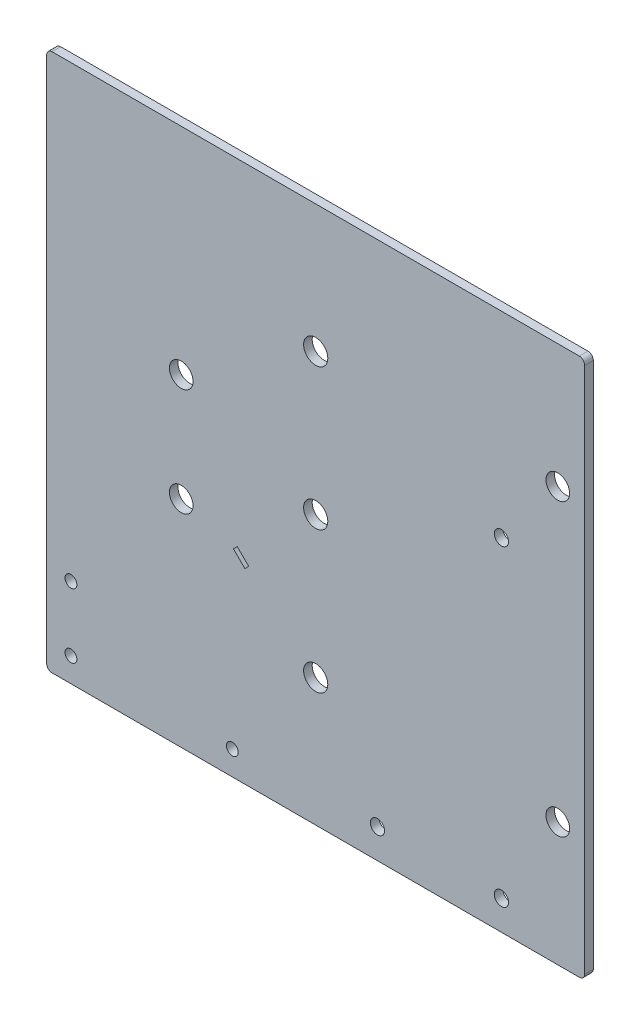
SolidWorks part; units mm, degrees
material "FR4_stuffedProtoboard"
ref_plane "Front Plane" through (0, 0, 0) normal (0, 0, 1) x (1, 0, 0)
ref_plane "Top Plane" through (0, 0, 0) normal (0, 1, 0) x (1, 0, 0)
ref_plane "Right Plane" through (0, 0, 0) normal (1, 0, 0) x (0, 0, -1)
sketch "Sketch1" plane through (0, 0, 0) normal (0, 0, 1) x (1, 0, 0)
  line L1 (-50, -50) -> (50, -50)
  line L2 (-50, -50) -> (-50, 50)
  line L3 (-50, 50) -> (50, 50)
  line L4 (50, -50) -> (50, 50)
  line L5 (-50, -50) -> (50, 50) construction
  line L6 (-50, 50) -> (50, -50) construction
  dimension "D1" = 100
extrude "Boss-Extrude1" add sketch "Sketch1" along normal blind 1.6
sketch "Sketch2" [suppressed] plane through (0, 0, 1.6) normal (0, 0, 1) x (1, 0, 0)
  circle A0 centre (0, 0) radius 50
  line M2 (50, -50) -> (50, 50)
  line M3 (50, 50) -> (-50, 50)
  line M4 (-50, 50) -> (-50, -50)
  line M5 (-50, -50) -> (50, -50)
  dimension "D1" = 100
extrude "Cut-Extrude1" [suppressed] cut sketch "Sketch2" against normal blind 1.6 contours A0 M3 M4 | A0 M4 M5 | A0 M5 M2 | A0 M2 M3
sketch "Sketch3" plane through (0, 0, 1.6) normal (0, 0, -1) x (-1, 0, 0)
  line L0 (-40, -22) -> (-50, -22) construction
  line L1 (-40, -32) -> (-40, -22) construction
  line L2 (-50, -32) -> (-40, -32) construction
  line L3 (-50, -22) -> (-50, -32) construction
  line L4 (-40, -22) -> (-50, -22)
  line L5 (-40, -32) -> (-40, -22)
  line L6 (-50, -32) -> (-40, -32)
  line L7 (-50, -22) -> (-50, -32)
  line L8 (-40, 22) -> (-40, 32) construction
  line L9 (-40, 32) -> (-50, 32) construction
  line L10 (-50, 32) -> (-50, 22) construction
  line L11 (-50, 22) -> (-40, 22) construction
  line L12 (-40, 22) -> (-40, 32)
  line L13 (-40, 32) -> (-50, 32)
  line L14 (-50, 32) -> (-50, 22)
  line L15 (-50, 22) -> (-40, 22)
  line L16 (5, -22) -> (-5, -22) construction
  line L17 (5, -32) -> (5, -22) construction
  line L18 (-5, -32) -> (5, -32) construction
  line L19 (-5, -22) -> (-5, -32) construction
  line L20 (5, -22) -> (-5, -22)
  line L21 (5, -32) -> (5, -22)
  line L22 (-5, -32) -> (5, -32)
  line L23 (-5, -22) -> (-5, -32)
  line L24 (5, 22) -> (5, 32) construction
  line L25 (5, 32) -> (-5, 32) construction
  line L26 (-5, 32) -> (-5, 22) construction
  line L27 (-5, 22) -> (5, 22) construction
  line L28 (5, 22) -> (5, 32)
  line L29 (5, 32) -> (-5, 32)
  line L30 (-5, 32) -> (-5, 22)
  line L31 (-5, 22) -> (5, 22)
  line L32 (17, 25) -> (45, 25) construction
  line L33 (45, 25) -> (45, -25) construction
  line L34 (17, -25) -> (45, -25) construction
  line L35 (17, 25) -> (17, -25) construction
  line L36 (17, 25) -> (45, 25)
  line L37 (45, 25) -> (45, -25)
  line L38 (17, -25) -> (45, -25)
  line L39 (17, 25) -> (17, -25)
  circle A0 centre (0, 26.25) radius 2.2479 construction
  circle A2 centre (0, 26.25) radius 2.2479
  circle A3 centre (0, 0) radius 2.2479
  circle A4 centre (-34.525, -44.525) radius 1.325 construction
  circle A6 centre (-34.525, -44.525) radius 1.325
  circle A8 centre (0, -26.25) radius 2.2479 construction
  circle A9 centre (0, -26.25) radius 2.2479
  circle A11 centre (-45, -27) radius 2.2
  circle A13 centre (-45, 27) radius 2.2
  circle A14 centre (-34.525, 13.525) radius 1.325 construction
  circle A15 centre (-34.525, 13.525) radius 1.325
  circle A16 centre (15.5, -45.5) radius 1.1 construction
  circle A17 centre (15.5, -45.5) radius 1.1
  circle A18 centre (45.5, -45.5) radius 1.1 construction
  circle A19 centre (45.5, -45.5) radius 1.1
  circle A20 centre (45.5, -33.5) radius 1.1 construction
  circle A21 centre (45.5, -33.5) radius 1.1
  circle A22 centre (-11.475, -44.525) radius 1.325 construction
  circle A23 centre (-11.475, -44.525) radius 1.325
  circle A24 centre (25, -10) radius 2.2 construction
  circle A25 centre (25, -10) radius 2.2
  circle A26 centre (25, 10) radius 2.2 construction
  circle A27 centre (25, 10) radius 2.2
  circle A28 centre (-45, 27) radius 2.2 construction
  circle A29 centre (-45, 27) radius 2.2
  circle A30 centre (-45, -27) radius 2.2 construction
  circle A31 centre (-45, -27) radius 2.2
  dimension "D1" = 4.4958
extrude "Cut-Extrude2" cut sketch "Sketch3" along normal through all contours A13 | A11 | A2 | A9 | A3 | A15 | A6 | A23 | A27 | A25 | A17 | A21 | A19 region at (0, 26.25, 1.6) region at (0, 0, 1.6) region at (34.525, -44.525, 1.6) region at (0, -26.25, 1.6) region at (45, -27, 1.6) region at (45, 27, 1.6) region at (34.525, 13.525, 1.6) region at (-15.5, -45.5, 1.6) region at (-45.5, -45.5, 1.6) region at (-45.5, -33.5, 1.6) region at (11.475, -44.525, 1.6) region at (-25, -10, 1.6) region at (-25, 10, 1.6)
sketch "Sketch4" plane through (0, 0, 1.6) normal (0, 0, 1) x (1, 0, 0)
  line L0 (38, -44.25) -> (38, -18.925) construction
  line L5 (38, -44.25) -> (38, -18.925)
  line L6 (11.75, -48) -> (34.25, -48) construction
  line L7 (11.75, -48) -> (34.25, -48)
  line L8 (8, -44.25) -> (8, 13.25) construction
  line L9 (8, -44.25) -> (8, 13.25)
  line L11 (33, -3) -> (33, -48) construction
  line L13 (34.25, 17) -> (11.75, 17)
  line L14 (38, 13.25) -> (38, -18.925)
  line L15 (-48, -48) -> (-13, -48) construction
  line L16 (-48, -48) -> (-13, -48)
  line L17 (-48, -31) -> (-48, -48) construction
  line L18 (-48, -31) -> (-48, -48)
  line L19 (-13, -40.5) -> (-13, -32.5) construction
  line L20 (-13, -40.5) -> (-13, -32.5)
  line L21 (-13, -48) -> (-13, -40.5) construction
  line L22 (-13, -48) -> (-13, -40.5)
  line L23 (-13, -32.5) -> (-13, -31) construction
  line L24 (-13, -32.5) -> (-13, -31)
  line L25 (-13, -31) -> (-48, -31) construction
  line L26 (-13, -31) -> (-48, -31)
  line L27 (-20, -34) -> (-20, -48) construction
  arc A0 (34.25, -48) -> (38, -44.25) centre (34.25, -44.25) ccw construction
  arc A1 (34.25, -48) -> (38, -44.25) centre (34.25, -44.25) ccw
  arc A2 (8, -44.25) -> (11.75, -48) centre (11.75, -44.25) ccw construction
  arc A3 (8, -44.25) -> (11.75, -48) centre (11.75, -44.25) ccw
  arc A4 (11.75, 17) -> (8, 13.25) centre (11.75, 13.25) ccw construction
  arc A5 (11.75, 17) -> (8, 13.25) centre (11.75, 13.25) ccw
  arc A6 (38, 13.25) -> (34.25, 17) centre (34.25, 13.25) ccw construction
  arc A7 (38, 13.25) -> (34.25, 17) centre (34.25, 13.25) ccw
  text T0 "Raspberry Pi Zero W" font "Century Gothic" height 2
  text T1 "Atheros" font "Century Gothic" height 2
  dimension "D1" = 5
  dimension "D2" = 20
  dimension "D3" = 3
  dimension "D4" = 7
fillet "Fillet1" radius 1 4 edges at (-50, -50, 0.8) (-50, 50, 0.8) (50, -50, 0.8) (50, 50, 0.8)
sketch "Sketch5" plane through (0, 0, 0) normal (0, 0, -1) x (-1, 0, 0)
  line L0 (-10, -30.25) -> (-10, -18.1401) construction
  line L5 (10, -18.1401) -> (10, -30.25) construction
  line L6 (-10, -30.25) -> (-10, -18.1401)
  line L7 (10, -18.1401) -> (10, -30.25)
  line L8 (-10, 18.1401) -> (-10, 30.25) construction
  line L9 (8, -32.25) -> (-8, -32.25) construction
  line L10 (-10, 18.1401) -> (-10, 30.25)
  line L11 (8, -32.25) -> (-8, -32.25)
  line L12 (-8, 32.25) -> (8, 32.25) construction
  line L13 (10, 30.25) -> (10, 18.1401) construction
  line L14 (-8, 32.25) -> (8, 32.25)
  line L15 (10, 30.25) -> (10, 18.1401)
  line L16 (12.4578, -14.5792) -> (14.5795, -12.4583)
  line L17 (14.5795, -12.4583) -> (15.2865, -13.1655)
  line L18 (15.2865, -13.1655) -> (13.1648, -15.2865)
  line L19 (13.1648, -15.2865) -> (12.4578, -14.5792)
  line L20 (14.2257, -14.226) -> (13.0417, -13.0416) construction
  arc A0 (-10, -18.1401) -> (-10.8966, -16.472) centre (-12, -18.1401) ccw construction
  arc A1 (10.7825, -16.5533) -> (10, -18.1401) centre (12, -18.1401) ccw construction
  arc A2 (16.5371, -10.7976) -> (10.8966, 16.472) centre (0, 0) ccw construction
  arc A3 (-10.8966, 16.472) -> (-10.8966, -16.472) centre (0, 0) ccw construction
  arc A4 (-10, -18.1401) -> (-10.8966, -16.472) centre (-12, -18.1401) ccw
  arc A5 (10.7825, -16.5533) -> (10, -18.1401) centre (12, -18.1401) ccw
  arc A6 (16.5371, -10.7976) -> (10.8966, 16.472) centre (0, 0) ccw
  arc A7 (-10.8966, 16.472) -> (-10.8966, -16.472) centre (0, 0) ccw
  arc A8 (-8, 32.25) -> (-10, 30.25) centre (-8, 30.25) ccw construction
  arc A9 (-10.8966, 16.472) -> (-10, 18.1401) centre (-12, 18.1401) ccw construction
  arc A10 (-10, -30.25) -> (-8, -32.25) centre (-8, -30.25) ccw construction
  arc A11 (-8, 32.25) -> (-10, 30.25) centre (-8, 30.25) ccw
  arc A12 (-10.8966, 16.472) -> (-10, 18.1401) centre (-12, 18.1401) ccw
  arc A13 (-10, -30.25) -> (-8, -32.25) centre (-8, -30.25) ccw
  arc A14 (8, -32.25) -> (10, -30.25) centre (8, -30.25) ccw construction
  arc A15 (8, -32.25) -> (10, -30.25) centre (8, -30.25) ccw
  arc A16 (10, 30.25) -> (8, 32.25) centre (8, 30.25) ccw construction
  arc A17 (10, 18.1401) -> (10.8966, 16.472) centre (12, 18.1401) ccw construction
  arc A18 (10, 30.25) -> (8, 32.25) centre (8, 30.25) ccw
  arc A19 (10, 18.1401) -> (10.8966, 16.472) centre (12, 18.1401) ccw
  spline S0 degree 3 poles (225.4005, 960.1445) (-563.1312, -917.0515) (826.4426, 674.9614) (-924.2551, -361.108) knots -32.721263 -32.721263 -32.721263 -32.721263 33.151256 33.151256 33.151256 33.151256 only from (10.7825, -16.5533) to (13.3154, -13.3154) construction
  spline S1 degree 3 poles (361.4613, 924.1243) (-675.4056, -825.875) (917.4584, 562.1807) (-960.4307, -224.1724) knots -32.327625 -32.327625 -32.327625 -32.327625 33.90185 33.90185 33.90185 33.90185 only from (13.3154, -13.3154) to (16.5386, -10.7986) construction
  spline S2 degree 3 poles (10.7825, -16.5533) (11.7399, -15.5684) (12.5904, -14.482) (13.3154, -13.3154) knots 0 0 0 0 1 1 1 1
  spline S3 degree 3 poles (13.3154, -13.3154) (14.4761, -12.5946) (15.5575, -11.7496) (16.5386, -10.7986) knots 0 0 0 0 1 1 1 1
  dimension "D1" = 1
  dimension "D2" = 3
extrude "Cut-Extrude4" cut sketch "Sketch5" against normal through all contours L18 L19 L16 L17
